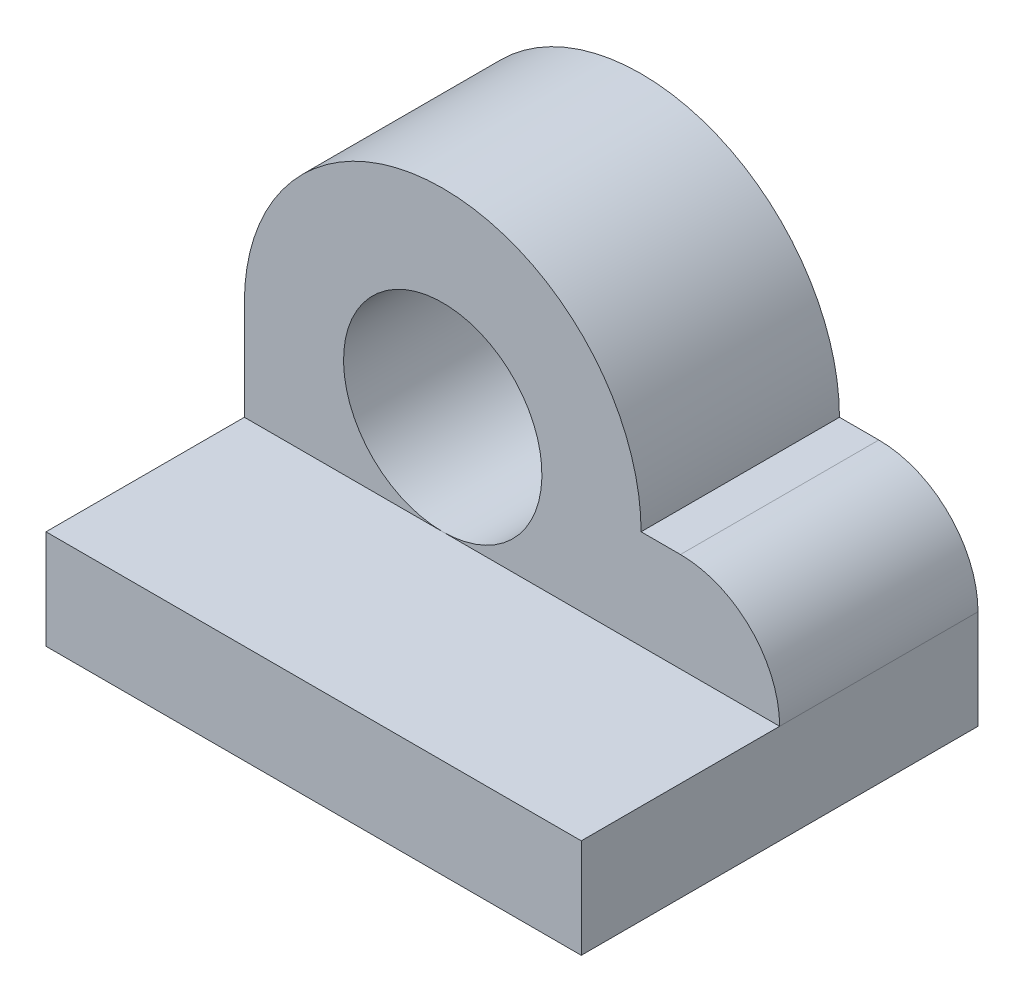
SolidWorks part; units mm, degrees
ref_plane "Front Plane" through (0, 0, 0) normal (0, 0, 1) x (1, 0, 0)
ref_plane "Top Plane" through (0, 0, 0) normal (0, 1, 0) x (1, 0, 0)
ref_plane "Right Plane" through (0, 0, 0) normal (1, 0, 0) x (0, 0, -1)
sketch "Sketch1" plane through (0, 0, 0) normal (0, 0, 1) x (1, 0, 0)
  line L0 (0, 0) -> (1370.7925, 0)
  line L1 (1370.7925, 0) -> (1370.7925, 254)
  line L2 (1116.7925, 508) -> (1016, 508)
  line L3 (0, 0) -> (0, 508)
  line L4 (0, 254) -> (1370.7925, 254)
  arc A0 (1370.7925, 254) -> (1116.7925, 508) centre (1116.7925, 254) ccw
  arc A1 (1016, 508) -> (0, 508) centre (508, 508) ccw
  circle A2 centre (508, 508) radius 254
  point P13 (1296.3976, 433.6051)
  dimension "D4" = 508
  dimension "D5" = 1016
  dimension "D1" = 508
  dimension "D2" = 1370.7925
  dimension "D3" = 254
  dimension "D6" = 254
extrude "Boss-Extrude1" add sketch "Sketch1" along normal blind 508 contours L4 A2 A0 L2 A1 L3 | L4 L3 L0 L1 region at (685.3963, 127, 0) region at (15.6835, 381, 0)
extrude "Boss-Extrude2" add sketch "Sketch1<4>" along normal blind 1016 contours L4 L3 L0 L1 region at (685.3963, 127, 0)
sketch "Sketch1<4>" plane through (0, 0, 0) normal (0, 0, 1) x (1, 0, 0) same geometry as "Sketch1"
